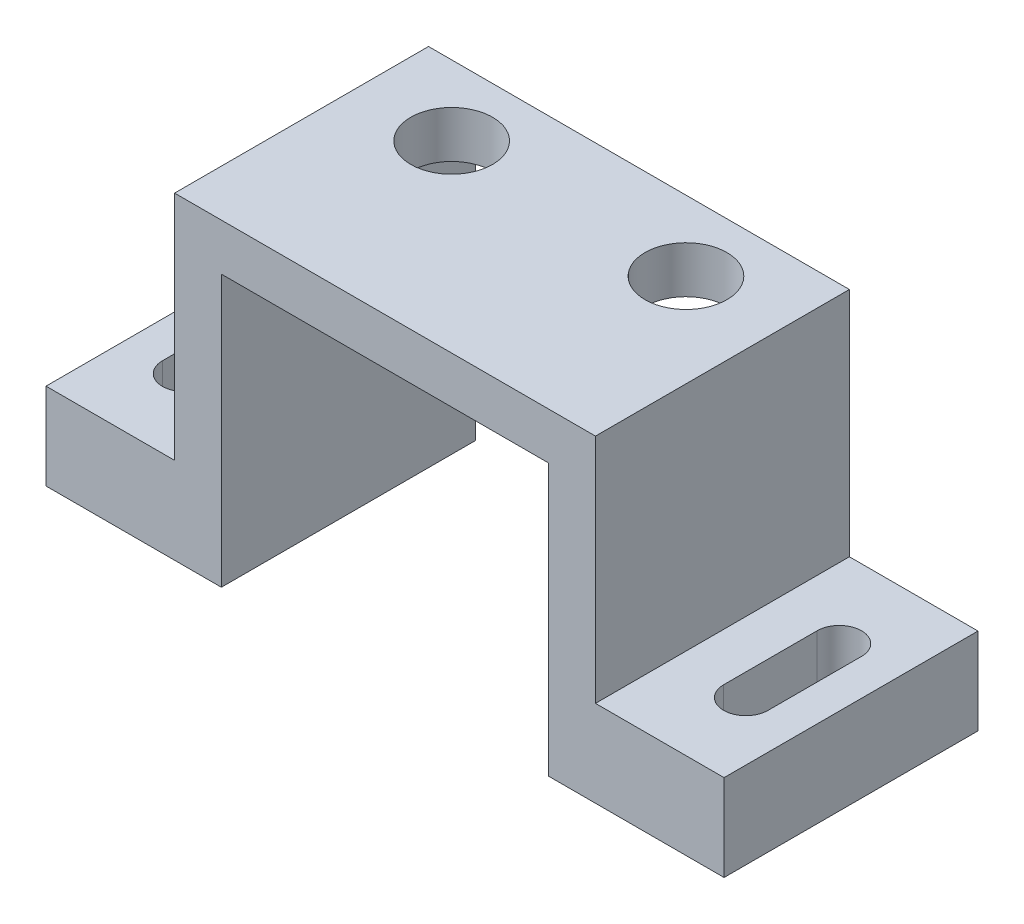
SolidWorks part; units mm, degrees
ref_plane "Front Plane" through (0, 0, 0) normal (0, 0, 1) x (1, 0, 0)
ref_plane "Top Plane" through (0, 0, 0) normal (0, 1, 0) x (1, 0, 0)
ref_plane "Right Plane" through (0, 0, 0) normal (1, 0, 0) x (0, 0, -1)
ref_axis "X-Axis" through (-88.99, 0, 0) along (1, 0, 0)
ref_axis "Y-Axis" through (0, 55, 0) along (0, -1, 0)
ref_axis "Z-Axis" through (0, 0, -88.99) along (0, 0, 1)
sketch "Sketch3" plane through (0, 0, 0) normal (0, 1, 0) x (1, 0, 0)
  line L1 (-9, -3) -> (9, -3)
  line L2 (-9, -3) -> (-9, 3)
  line L3 (-9, 3) -> (9, 3)
  line L4 (9, -3) -> (9, 3)
  line L5 (-9, -3) -> (9, 3) construction
  line L6 (-9, 3) -> (9, -3) construction
  point P0 (0, 0)
  dimension "D1" = 18
  dimension "D2" = 6
extrude "Boss-Extrude1" add sketch "Sketch3" along normal blind 2
sketch "Sketch4" plane through (0, 2, 0) normal (0, 1, 0) x (1, 0, 0)
  line L0 (-9, 0) -> (9, 0) construction
  line L1 (-9, 3) -> (-9, -3) construction
  line L2 (9, -3) -> (9, 3) construction
  line L3 (5.01, 0) -> (-5.01, 0) construction
  circle A0 centre (-5.01, 0) radius 1.75
  circle A1 centre (5.01, 0) radius 1.75
  point P12 (0, 0)
  dimension "D1" = 3.5
  dimension "D2" = 10.02
extrude "Cut-Extrude1" cut sketch "Sketch4" against normal through all
sketch "Sketch5" plane through (0, 0, 0) normal (0, 1, 0) x (1, 0, 0)
  line L1 (-9, -3) -> (9, -3)
  line L2 (-9, -3) -> (-9, -7.86)
  line L3 (-9, -7.86) -> (9, -7.86)
  line L4 (9, -3) -> (9, -7.86)
  circle A0 centre (-5.01, 0) radius 1.75 construction
  dimension "D1" = 7.86
extrude "Boss-Extrude4" add sketch "Sketch5" along normal up to surface (2 mm away) up to face at (-5.01, 2, 1.75)
sketch "Sketch6" plane through (0, 0, 0) normal (0, -1, 0) x (1, 0, 0)
  line L0 (9, -3) -> (-9, -3) construction
  line L1 (-9, 7.86) -> (-7, 7.86)
  line L2 (-9, 7.86) -> (-9, -3)
  line L3 (-9, -3) -> (-7, -3)
  line L4 (-7, 7.86) -> (-7, -3)
  dimension "D1" = 2
extrude "Boss-Extrude5" add sketch "Sketch6" along normal blind 11.6
sketch "Sketch7" plane through (-9, 0, 0) normal (-1, 0, 0) x (0, 0, 1)
  line L0 (7.86, 2) -> (7.86, -11.6) construction
  line L1 (-3, -11.6) -> (7.86, -11.6)
  line L2 (-3, -11.6) -> (-3, -7.9)
  line L3 (-3, -7.9) -> (7.86, -7.9)
  line L4 (7.86, -11.6) -> (7.86, -7.9)
  dimension "D1" = 3.7
extrude "Boss-Extrude6" add sketch "Sketch7" along normal blind 5.5
sketch "Sketch8" plane through (0, -7.9, 0) normal (0, 1, 0) x (1, 0, 0)
  line L0 (-12, 3) -> (-12, -0.43) construction
  line L1 (-14.5, 3) -> (-9, 3) construction
  line L2 (-12, -0.43) -> (-12, -4.43) construction
  line L3 (-12, -4.43) -> (-12, -7.86) construction
  line L4 (-14.5, -7.86) -> (-9, -7.86) construction
  line L5 (-12, -0.43) -> (-12, -4.43) construction
  line L6 (-11.05, -0.43) -> (-11.05, -4.43)
  line L7 (-12.95, -0.43) -> (-12.95, -4.43)
  line L8 (-14.5, -7.86) -> (-14.5, 3) construction
  arc A0 (-11.05, -0.43) -> (-12.95, -0.43) centre (-12, -0.43) ccw
  arc A1 (-12.95, -4.43) -> (-11.05, -4.43) centre (-12, -4.43) ccw
  point P8 (-12, -2.43)
  dimension "D2" = 0.95
  dimension "D1" = 2.5
  dimension "D3" = 4
extrude "Cut-Extrude2" cut sketch "Sketch8" against normal through all
mirror "Mirror1" about plane through (0, 0, 0) normal (1, 0, 0) of "Cut-Extrude2", "Boss-Extrude4", "Boss-Extrude6", "Boss-Extrude5"
equation "\"D2@Sketch8\"=1.90mm/2"
